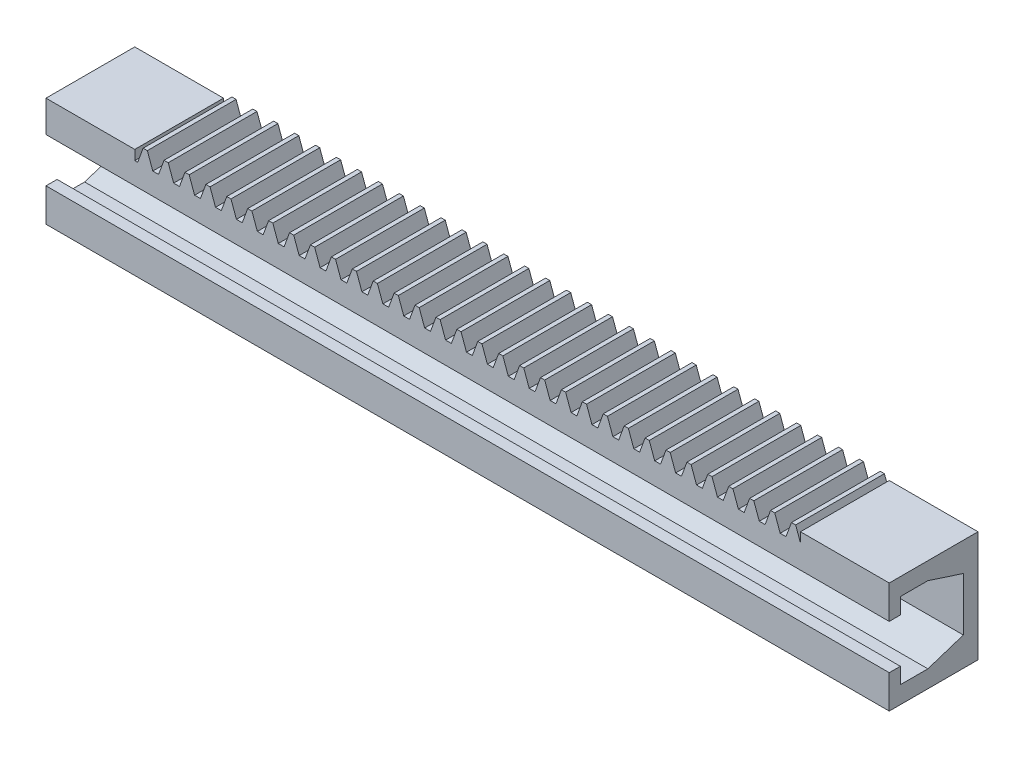
SolidWorks part; units mm, degrees
extrude "Blank" add sketch "BlankSke" against normal blind 20
sketch "BlankSke" plane through (0, 0, 0) normal (0, 0, 1) x (1, 0, 0)
  line L1 (0, 0) -> (150, 0)
  line L2 (0, 0) -> (0, 11.5)
  line L3 (0, 11.5) -> (150, 11.5)
  line L4 (150, 0) -> (150, 11.5)
  dimension "Length" = 150
ref_plane "Plane1" through (0, 0, 0) normal (0, 0, 1) x (1, 0, 0)
ref_plane "Plane2" through (0, 0, 0) normal (0, 1, 0) x (1, 0, 0)
ref_plane "Plane3" through (0, 0, 0) normal (1, 0, 0) x (0, 0, -1)
other "Configuration Table"
sketch "HoldingSke" plane through (0, 0, 0) normal (0, 1, 0) x (1, 0, 0)
  line L0 (0, 0) -> (0.0928, 0.6602)
  line L1 (-15, 0) -> (100, 0) construction
  line L2 (0, 0) -> (-2.1039, 2.3779)
  line L3 (0, 0) -> (-11.863, 4.5341)
  line L4 (0, 0) -> (7.2428, 4.7035)
  line L5 (0, 0) -> (-23.7986, -8.8762)
  line L6 (0, 0) -> (-10.5278, -7.1032)
  line L9 (-71.009, 38.7566) -> (69.9449, 90.0596)
  line L10 (-76.2, 3.8779) -> (-66.2, 3.8779)
  line L11 (0, 0) -> (-20, 0)
  line L12 (-76.2, 101.6) -> (-76.147, 101.6)
  line L13 (24.9733, 27.94) -> (52.9518, 28.4284)
  line L14 (24.9733, 27.94) -> (24.9743, 27.94)
  line L15 (24.9733, 27.94) -> (100.4006, 29.5858)
  circle A0 centre (0, 0) radius 19.05
  circle A1 centre (0, 0) radius 5
  circle A2 centre (0, 0) radius 12.7
  dimension "Num_teeth" = 33
  dimension "Width" = 20
  dimension "Length" = 150
  dimension "Pitch_height" = 10
sketch "TooCutSkeIll" plane through (0, 0, 0) normal (0, 0, 1) x (1, 0, 0)
  line L0 (-1.8687, 11.4605) -> (-0.7447, 8.3724)
  line L1 (-0.3914, 8.125) -> (0.3914, 8.125)
  line L2 (0.7447, 8.3724) -> (1.8687, 11.4605)
  line L3 (150, 11.5) -> (0, 11.5) construction
  line L4 (0, 0) -> (0, 64.897) construction
  line L5 (-13.208, 10) -> (12.954, 10) construction
  line L6 (0, 0) -> (150, 0) construction
  line L7 (1.3371, 10) -> (1.3371, 48.7463) construction
  line L8 (-1.3371, 10) -> (-1.3371, 48.7463) construction
  line L9 (1.9251, 11.5) -> (1.9251, 11.5254)
  line L10 (-1.9251, 11.5) -> (-1.9251, 11.5254)
  line L11 (-1.9251, 11.5254) -> (1.9251, 11.5254)
  arc A0 (0.3914, 8.125) -> (0.7447, 8.3724) centre (0.3914, 8.501) ccw
  arc A1 (-0.7447, 8.3724) -> (-0.3914, 8.125) centre (-0.3914, 8.501) ccw
  arc A2 (1.9251, 11.5) -> (1.8687, 11.4605) centre (1.9251, 11.44) ccw
  arc A3 (-1.8687, 11.4605) -> (-1.9251, 11.5) centre (-1.9251, 11.44) ccw
  dimension "Addendum_plus" = 1.5254
  dimension "Pitch_height" = 10
  dimension "Pressure_angle" = 20
  dimension "Gap_width" = 2.6742
  dimension "Dedendum" = 1.875
extrude "ToothCutIll" [suppressed] cut sketch "TooCutSkeIll" against normal through all
sketch "TooCutSkeSim" plane through (0, 0, 0) normal (0, 0, 1) x (1, 0, 0)
  line L0 (0.6547, 8.125) -> (-0.6547, 8.125)
  line L1 (1.8923, 11.5254) -> (0.6547, 8.125)
  line L2 (0, 17.4625) -> (0, 53.467) construction
  line L3 (1.8923, 11.5254) -> (-1.8923, 11.5254)
  line L6 (-1.8923, 11.5254) -> (-0.6547, 8.125)
  line L9 (-1.3371, 10) -> (1.3371, 10) construction
  line L10 (0, 0) -> (150, 0) construction
  line L11 (1.3371, 10) -> (1.3371, 53.467) construction
  line L12 (-1.3371, 10) -> (-1.3371, 53.467) construction
  dimension "Addendum_plus" = 1.5254
  dimension "Pitch_height" = 10
  dimension "Pressure_angle" = 20
  dimension "Gap_width" = 2.6742
  dimension "Dedendum" = 1.875
extrude "ToothCutSim" cut sketch "TooCutSkeSim" against normal through all
pattern_linear "TeethCuts" count 33 spacing 4.7124 along (1, 0, 0) of "ToothCutIll", "ToothCutSim"
sketch "Sketch1" plane through (150, 0, 0) normal (1, 0, 0) x (0, 0, -1)
  line L0 (0, 8.5146) -> (0, 10.7146)
  line L1 (0, 8.5146) -> (0, 11.5) construction
  line L2 (0, 10.7146) -> (20, 10.7146)
  line L3 (20, 11.5) -> (20, 8.5146) construction
  line L7 (0, 8.5146) -> (0, 0)
  line L8 (0, 0) -> (20, 0)
  line L9 (20, 0) -> (20, 10.7146)
extrude "Boss-Extrude1" add sketch "Sketch1" along normal blind 20
sketch "Sketch2" plane through (0, 0, 0) normal (-1, 0, 0) x (0, 0, 1)
  line L0 (-20, 8.125) -> (-20, 10.325)
  line L1 (-20, 8.125) -> (-20, 11.5) construction
  line L2 (-20, 10.325) -> (0, 10.325)
  line L3 (0, 8.125) -> (0, 11.5) construction
  line L4 (0, 10.325) -> (0, 0)
  line L5 (0, 0) -> (-20, 0)
  line L6 (-20, 0) -> (-20, 8.125)
extrude "Boss-Extrude2" add sketch "Sketch2" along normal blind 20
sketch "Sketch3" plane through (0, 0, 0) normal (0, -1, 0) x (1, 0, 0)
  line L1 (-20, 0) -> (170, 0)
  line L2 (-20, 0) -> (-20, -20)
  line L3 (-20, -20) -> (170, -20)
  line L4 (170, 0) -> (170, -20)
extrude "Boss-Extrude3" add sketch "Sketch3" along normal blind 14.285
sketch "Sketch4" plane through (170, 0, 0) normal (1, 0, 0) x (0, 0, -1)
  line L2 (0, 10.7146) -> (0, -14.285) construction
  line L4 (2.5, -10.3852) -> (2.5, -6.7852)
  line L5 (2.5, 6.8148) -> (8.7, 6.8148)
  line L7 (16.7, 4.2148) -> (16.7, -7.7852)
  line L8 (16.7, -7.7852) -> (8.7, -10.3852)
  line L9 (16.7, -1.7852) -> (16.7, 4.2148)
  line L10 (16.7, 4.2148) -> (8.7, 6.8148)
  line L11 (2.5, -10.3852) -> (8.7, -10.3852)
  line L12 (0, -1.7852) -> (0, 3.2148)
  line L13 (0, 3.2148) -> (2.5, 3.2148)
  line L15 (2.5, -6.7852) -> (0, -6.7852)
  line L16 (0, -6.7852) -> (0, 3.2148)
  line L17 (2.5, 3.2148) -> (2.5, 6.8148)
  line M11 (0, 10.7146) -> (0, -14.285)
extrude "Cut-Extrude1" cut sketch "Sketch4" against normal through all contours L17 L13 L15 L4 L11 L8 L7 L10 L5 M11 region at (170, -1.7852, -8.3886)
equation "' \"Module@HoldingSke\" = 6.35"
equation "' \"Num_teeth@HoldingSke\" = 12"
equation "' \"Ap@HoldingSke\" =  20"
equation "' \"Ap@HoldingSke\" = 20"
equation "' \"Width@HoldingSke\" = 0.25 * 25.4"
equation "' \"Show_teeth@HoldingSke\" = 500"
equation "' \"Backlash@HoldingSke\" = 0.009 * 25.4"
equation "' \"Addendum_fac@HoldingSke\" = 1.0"
equation "' \"Dedendum_fac@HoldingSke\" = 1.25"
equation "' \"Dedendum_add@HoldingSke\" = 0.00005 * 25.4"
equation "' \"Clearance_fac@HoldingSke\" = 0.25"
equation "' \"Pitch_height@HoldingSke\" = 1 * 25.4"
equation "' \"Length@HoldingSke\" = 4.71 * 25.4"
equation "\"Pitch@HoldingSke\" = 1 / \"Module@HoldingSke\""
equation "\"MPH@HoldingSke\" = \"Dedendum_fac@HoldingSke\" / \"Pitch@HoldingSke\" + 2 * \"Dedendum_add@HoldingSke\" + 0.002 * 25.4"
equation "\"MPH@HoldingSke\" = ((sgn( \"MPH@HoldingSke\" - \"Pitch_height@HoldingSke\")+1)*( \"MPH@HoldingSke\" - \"Pitch_height@HoldingSke\"))/2 + \"Pitch_height@HoldingSke\""
equation "\"Blank_height@BlankSke\" = \"Pitch_height@HoldingSke\" + \"Addendum_fac@HoldingSke\"  / \"Pitch@HoldingSke\" "
equation "\"Length@BlankSke\" =  \"Length@HoldingSke\""
equation "\"Face_width@Blank\" = \"Width@HoldingSke\""
equation "\"Pressure_angle@TooCutSkeIll\" = \"Ap@HoldingSke\""
equation "\"Addendum_plus@TooCutSkeIll\" =  \"Addendum_fac@HoldingSke\"  / \"Pitch@HoldingSke\" + 0.001 *25.4"
equation "\"Dedendum@TooCutSkeIll\" = \"Dedendum_fac@HoldingSke\"  / \"Pitch@HoldingSke\""
equation "\"Pitch_height@TooCutSkeIll\" =  \"MPH@HoldingSke\""
equation "\"Gap_width@TooCutSkeIll\" = 3.14159265 / 2 / \"Pitch@HoldingSke\" + 6 * \"Backlash@HoldingSke\""
equation "\"Pressure_angle@TooCutSkeSim\" = \"Ap@HoldingSke\""
equation "\"Addendum_plus@TooCutSkeSim\" =  \"Addendum_fac@HoldingSke\"  / \"Pitch@HoldingSke\" + 0.001 * 25.4"
equation "\"Dedendum@TooCutSkeSim\" = \"Dedendum_fac@HoldingSke\"  / \"Pitch@HoldingSke\""
equation "\"Pitch_height@TooCutSkeSim\" =  \"MPH@HoldingSke\""
equation "\"Gap_width@TooCutSkeSim\" = 3.14159265 / 2 / \"Pitch@HoldingSke\" + 6 * \"Backlash@HoldingSke\""
equation "\"Root_fillet@TooCutSkeIll\" = \"Clearance_fac@HoldingSke\" / \"Pitch@HoldingSke\" + \"Dedendum_add@HoldingSke\""
equation "\"Break_rad@TooCutSkeIll\" = 0.02 / \"Pitch@HoldingSke\" * 2"
equation "\"Linear_pitch@TeethCuts\" = 3.14159265 / \"Pitch@HoldingSke\""
equation "\"Num_teeth@HoldingSke\" = int( ( \"Length@HoldingSke\" + 0 ) / (3.14159265 / \"Pitch@HoldingSke\")) + 0.9999  + 1"
equation " \"Num_teeth@TeethCuts\" = int( \"Show_teeth@HoldingSke\" ) + 1"
equation " \"Num_teeth@TeethCuts\" = ((sgn( \"Num_teeth@TeethCuts\" - \"Num_teeth@HoldingSke\" )-1)*( \"Num_teeth@TeethCuts\" - \"Num_teeth@HoldingSke\" ))/-2+ \"Num_teeth@HoldingSke\""
equation " \"Num_teeth@TeethCuts\" = ((sgn( \"Num_teeth@TeethCuts\" - 2.0)+1)*( \"Num_teeth@TeethCuts\" - 2.0))/2 +2.0"
